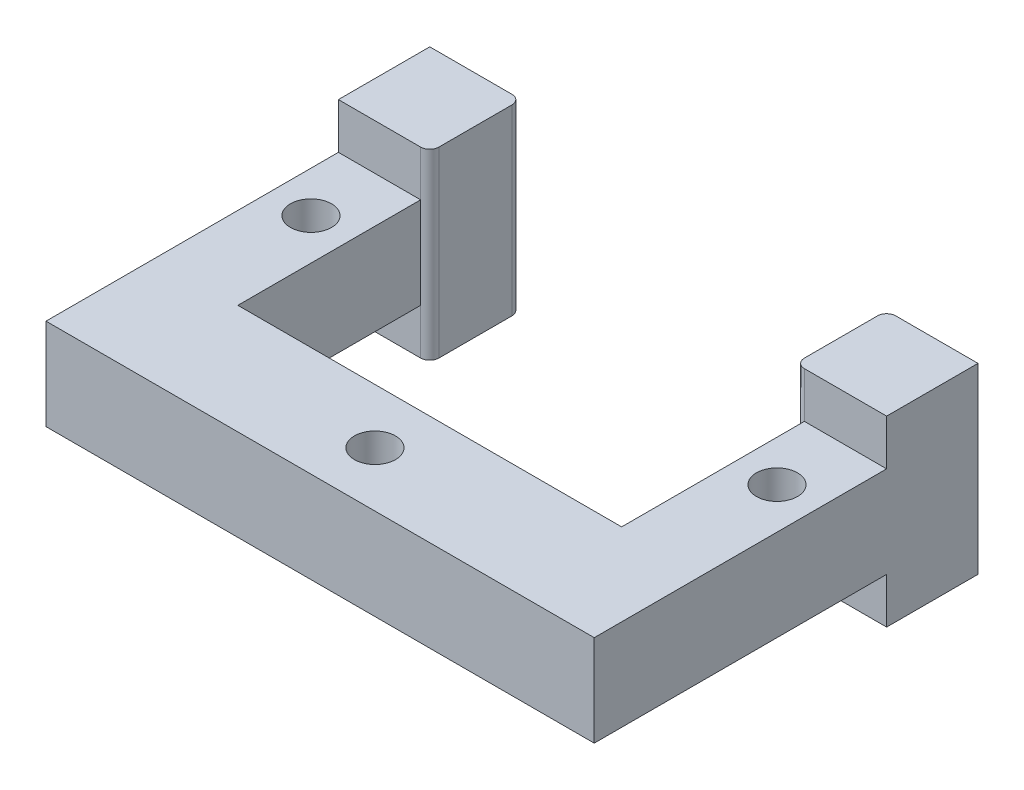
SolidWorks part; units mm, degrees
material "ABS"
ref_plane "Front Plane" through (0, 0, 0) normal (0, 0, 1) x (1, 0, 0)
ref_plane "Top Plane" through (0, 0, 0) normal (0, 1, 0) x (1, 0, 0)
ref_plane "Right Plane" through (0, 0, 0) normal (1, 0, 0) x (0, 0, -1)
sketch "Sketch1" plane through (0, 0, 0) normal (0, 1, 0) x (1, 0, 0)
  line L0 (0, 30.876) -> (0, -57.2152) construction
  line L1 (-20, 0) -> (-30, 0)
  line L2 (-30, 0) -> (-30, -42)
  line L3 (-30, -42) -> (30, -42)
  line L4 (30, -42) -> (30, 0)
  line L5 (30, 0) -> (20, 0)
  line L6 (20, 0) -> (20, -10)
  line L7 (20, -30) -> (-20, -30)
  line L8 (-20, -10) -> (-20, 0)
  line L9 (-20, -10) -> (-21, -10)
  line L10 (-21, -10) -> (-21, -30)
  line L11 (-21, -30) -> (-20, -30)
  line L12 (21, -30) -> (20, -30)
  line L13 (20, -10) -> (21, -10)
  line L14 (21, -10) -> (21, -30)
  point P5 (-25, 0)
  dimension "D1" = 40
  dimension "D2" = 10
  dimension "D3" = 30
  dimension "D4" = 12
  dimension "D5" = 10
  dimension "D6" = 1
extrude "Boss-Extrude1" add sketch "Sketch1" along normal blind 20
sketch "Sketch2" plane through (0, 0, 0) normal (0, 0, -1) x (-1, 0, 0)
  line L0 (-25, 20) -> (-25, 0) construction
  line L1 (-30, 20) -> (-20, 20) construction
  line L2 (-30, 0) -> (-20, 0) construction
  line L4 (0, 0) -> (0, 42.0055) construction
  circle A2 centre (-24.25, 14.79) radius 2.75
  circle A3 centre (-24.25, 4.79) radius 2.75
  point P6 (-24.25, 14.79)
  point P11 (-24.25, 4.79)
  dimension "D4" = 5.5
  dimension "D1" = 5.21
  dimension "D2" = 24.25
  dimension "D3" = 15.21
extrude "Cut-Extrude1" cut sketch "Sketch2" against normal blind 8
mirror "Mirror1" about plane through (0, 0, 0) normal (1, 0, 0) of "Cut-Extrude1"
fillet "Fillet1" radius 1 4 edges at (-20, 10, 0) (20, 10, 0) (20, 10, 10) (-20, 10, 10)
sketch "Sketch7" plane through (0, 0, 0) normal (0, -1, 0) x (1, 0, 0)
  line L0 (-21, 10) -> (-30, 10)
  line L1 (21, 10) -> (30, 10)
  line L10 (21, 30) -> (21, 10)
  line L11 (20, 9) -> (20, 1)
  line L12 (21, 0) -> (30, 0)
  line L13 (30, 0) -> (30, 42)
  line L14 (30, 42) -> (-30, 42)
  line L15 (-30, 42) -> (-30, 0)
  line L16 (-30, 0) -> (-21, 0)
  line L17 (-20, 1) -> (-20, 9)
  line L18 (-21, 10) -> (-21, 30)
  line L19 (-21, 30) -> (21, 30)
  line L20 (21, 30) -> (21, 10)
  line L21 (20, 9) -> (20, 1)
  line L22 (21, 0) -> (30, 0)
  line L23 (30, 0) -> (30, 42)
  line L24 (30, 42) -> (-30, 42)
  line L25 (-30, 42) -> (-30, 0)
  line L26 (-30, 0) -> (-21, 0)
  line L27 (-20, 1) -> (-20, 9)
  line L28 (-21, 10) -> (-21, 30)
  line L29 (-21, 30) -> (21, 30)
  arc A4 (21, 10) -> (20, 9) centre (21, 9) ccw
  arc A5 (20, 1) -> (21, 0) centre (21, 1) ccw
  arc A6 (-21, 0) -> (-20, 1) centre (-21, 1) ccw
  arc A7 (-20, 9) -> (-21, 10) centre (-21, 9) ccw
  arc A8 (21, 10) -> (20, 9) centre (21, 9) ccw
  arc A9 (20, 1) -> (21, 0) centre (21, 1) ccw
  arc A10 (-21, 0) -> (-20, 1) centre (-21, 1) ccw
  arc A11 (-20, 9) -> (-21, 10) centre (-21, 9) ccw
  line M15 (21, 30) -> (21, 10)
  line M20 (30, 0) -> (30, 42)
  line M21 (30, 42) -> (-30, 42)
  line M22 (-30, 42) -> (-30, 0)
  line M27 (-21, 10) -> (-21, 30)
  line M28 (-21, 30) -> (21, 30)
  dimension "D1" = 0
extrude "Cut-Extrude3" cut sketch "Sketch7" against normal blind 5 contours L1 L0 M15 M20 M21 M22 M27 M28 region at (0, 0, 30.6667)
ref_plane "Plane2" through (0, 10, 0) normal (0, 1, 0) x (1, 0, 0)
mirror "Mirror2" about plane through (0, 10, 0) normal (0, 1, 0) of "Cut-Extrude3"
sketch "Sketch8" plane through (0, 15, 0) normal (0, 1, 0) x (1, 0, 0)
  line L8 (21, -10) -> (21, -30)
  line L9 (21, -30) -> (-21, -30)
  line L10 (-21, -30) -> (-21, -10)
  line L11 (-21, -10) -> (-30, -10)
  line L12 (-30, -10) -> (-30, -42)
  line L13 (-30, -42) -> (30, -42)
  line L14 (30, -42) -> (30, -10)
  line L15 (30, -10) -> (21, -10)
  line L16 (21, -10) -> (21, -30)
  line L17 (21, -30) -> (-21, -30)
  line L18 (-21, -30) -> (-21, -10)
  line L19 (-21, -10) -> (-30, -10)
  line L20 (-30, -10) -> (-30, -42)
  line L21 (-30, -42) -> (30, -42)
  line L22 (30, -42) -> (30, -10)
  line L23 (30, -10) -> (21, -10)
  dimension "D1" = 0
sketch "Sketch9" plane through (0, 5, 0) normal (0, -1, 0) x (1, 0, 0)
  line L0 (-30, 36) -> (30, 36) construction
  line L1 (-25.5, 10) -> (-25.5, 42) construction
  line L2 (0, 51.8317) -> (0, -8.1141) construction
  line L8 (21, 30) -> (21, 10)
  line L9 (21, 10) -> (30, 10)
  line L10 (30, 10) -> (30, 42)
  line L11 (30, 42) -> (-30, 42)
  line L12 (-30, 42) -> (-30, 10)
  line L13 (-30, 10) -> (-21, 10)
  line L14 (-21, 10) -> (-21, 30)
  line L15 (-21, 30) -> (21, 30)
  line L16 (21, 30) -> (21, 10)
  line L17 (21, 10) -> (30, 10)
  line L18 (30, 10) -> (30, 42)
  line L19 (30, 42) -> (-30, 42)
  line L21 (-30, 10) -> (-21, 10)
  line L23 (-21, 30) -> (21, 30)
  circle A0 centre (0, 36) radius 2.25
  circle A1 centre (-25.5, 17.5) radius 2.25
  circle A2 centre (25.5, 17.5) radius 2.25
  dimension "D2" = 4.5
  dimension "D3" = 7.5
  dimension "D1" = 0
extrude "Cut-Extrude5" cut sketch "Sketch9" against normal through all contours A1 | A2 | A0 region at (-25.5, 5, 17.5) region at (25.5, 5, 17.5)
